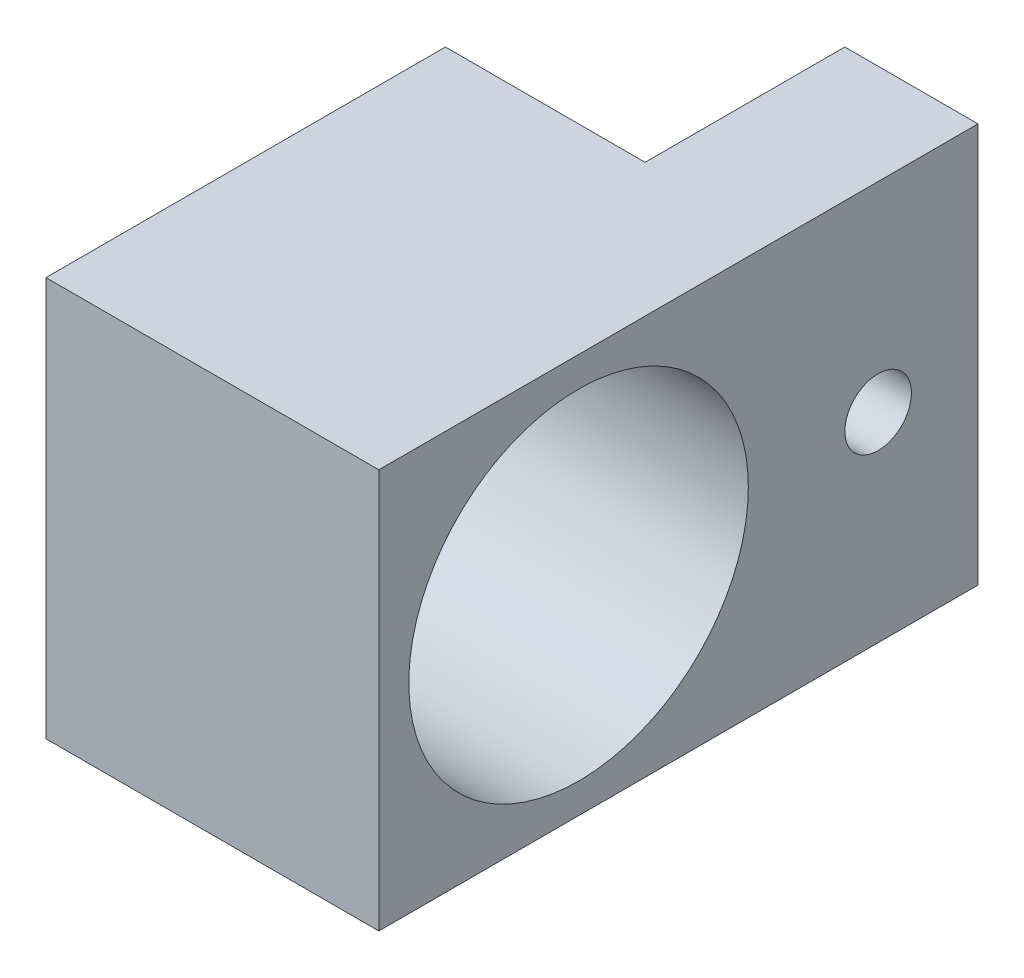
SolidWorks part; units mm, degrees
ref_plane "Front Plane" through (0, 0, 0) normal (1, 0, 0) x (0, 1, 0)
ref_plane "Top Plane" through (0, 0, 0) normal (0, 0, 1) x (0, 1, 0)
ref_plane "Right Plane" through (0, 0, 0) normal (0, 1, 0) x (-1, 0, 0)
sketch "Sketch1" plane through (0, 0, 0) normal (0, 0, 1) x (0, 1, 0)
  line L1 (0, 0) -> (30, 0)
  line L2 (0, 0) -> (0, 15)
  line L3 (0, 15) -> (30, 15)
  line L4 (30, 0) -> (30, 15)
  dimension "D1" = 15
  dimension "D2" = 30
extrude "Boss-Extrude1" add sketch "Sketch1" along normal blind 30 contours L1 L4 L3 L2
sketch "Sketch2" plane through (0, 0, 0) normal (1, 0, 0) x (0, 1, 0)
  line L1 (0, 30) -> (30, 30)
  line L2 (0, 30) -> (0, -15)
  line L3 (0, -15) -> (30, -15)
  line L4 (30, 30) -> (30, -15)
  line L6 (30, 30) -> (30, 0) construction
  line L7 (0, 0) -> (30, 0) construction
  point P7 (30, 0)
  dimension "D1" = 15
extrude "Boss-Extrude2" add sketch "Sketch2" along normal blind 10
sketch "Sketch3" plane through (10, 0, 0) normal (1, 0, 0) x (0, 1, 0)
  line L3 (30, 30) -> (0, 30) construction
  line L12 (15, 15) -> (15, 30)
  circle A2 centre (15, 15) radius 15
  circle A3 centre (15, 15) radius 12.75
  dimension "D1" = 30
sketch "Sketch5" plane through (10, 0, 0) normal (1, 0, 0) x (0, 1, 0)
  line L0 (0, 0) -> (30, 0) construction
  line L2 (30, -15) -> (30, 0) construction
  circle A0 centre (15, -7.5) radius 2.5
  dimension "D1" = 5
  dimension "D2" = 7.5
  dimension "D3" = 15
extrude "Cut-Extrude2" cut sketch "Sketch5" against normal through all
extrude "Cut-Extrude3" cut sketch "Sketch3" against normal through all contours A3
sketch "Sketch8" plane through (0, 0, 0) normal (0, 0, -1) x (1, 0, 0)
  line L0 (0, 0) -> (-15, 0) construction
  line L1 (-15, 0) -> (-15, -30) construction
  circle A0 centre (-7.5, -15) radius 2.5
  dimension "D1" = 5
  dimension "D2" = 15
  dimension "D3" = 7.5
extrude "Cut-Extrude4" cut sketch "Sketch8" against normal blind 10
